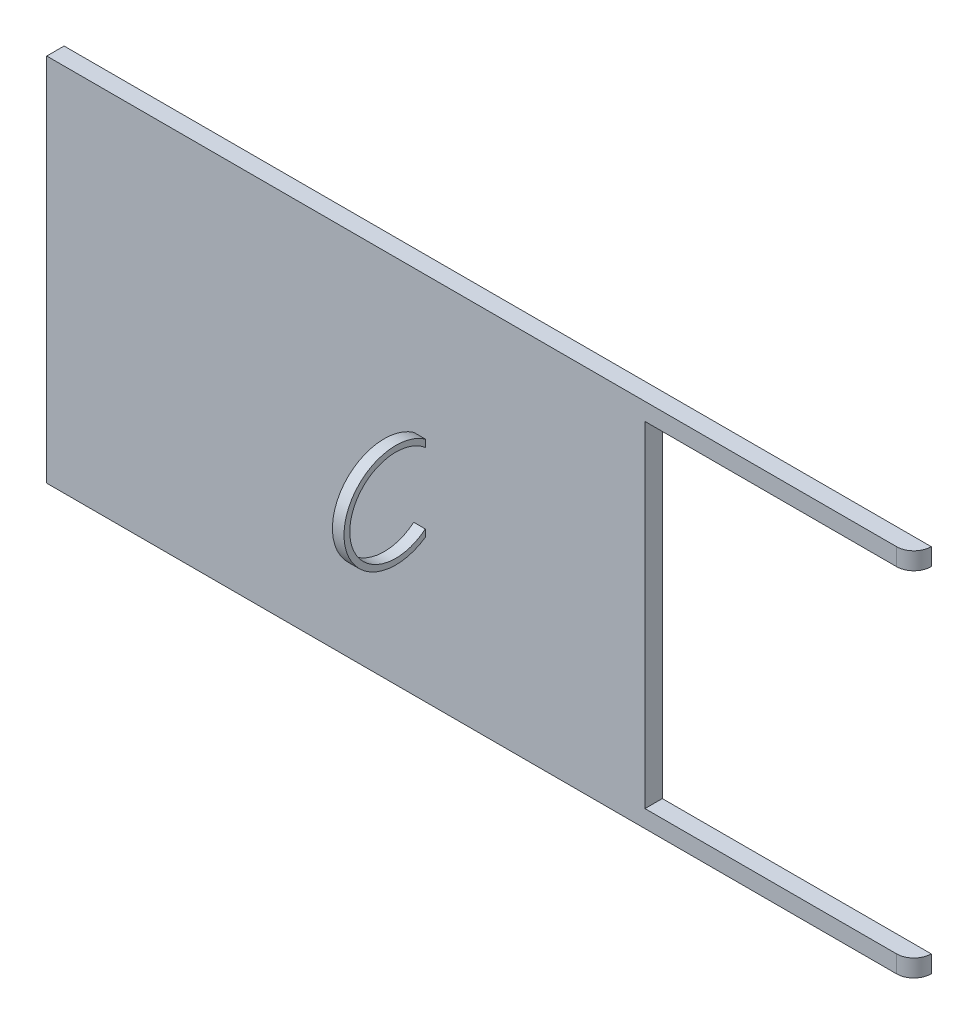
SolidWorks part; units mm, degrees
ref_plane "Top plane" through (0, 0, 0) normal (0, 0, 1) x (1, 0, 0)
ref_plane "Right plane" through (0, 0, 0) normal (0, 1, 0) x (1, 0, 0)
ref_plane "Front plane" through (0, 0, 0) normal (1, 0, 0) x (0, 0, -1)
sketch "Sketch1" plane through (0, 0, 0) normal (0, 0, 1) x (1, 0, 0)
  line L1 (-40, 113.7342) -> (63.4793, 113.7342)
  line L2 (-40, 113.7342) -> (-40, 49.7342)
  line L3 (-40, 49.7342) -> (63.4793, 49.7342)
  line L4 (63.4793, 113.7342) -> (63.4793, 49.7342)
extrude "Boss-Extrude1" add sketch "Sketch1" along normal blind 3
sketch "Sketch2" plane through (0, 0, 3) normal (0, 0, 1) x (1, 0, 0)
  line L0 (63.4793, 49.7342) -> (63.4793, 113.7342) construction
  line L1 (63.4793, 113.7342) -> (-40, 113.7342) construction
  line L2 (63.4793, 113.7342) -> (110, 113.7342)
  line L3 (63.4793, 113.7342) -> (63.4793, 110.7342)
  line L4 (63.4793, 110.7342) -> (110, 110.7342)
  line L5 (110, 113.7342) -> (110, 110.7342)
  line L7 (63.4793, 49.7342) -> (110, 49.7342)
  line L8 (63.4793, 49.7342) -> (63.4793, 52.7342)
  line L9 (63.4793, 52.7342) -> (110, 52.7342)
  line L10 (110, 49.7342) -> (110, 52.7342)
extrude "Boss-Extrude2" add sketch "Sketch2" against normal up to surface (3 mm away)
fillet "Fillet1" radius 3 2 edges at (110, 51.2342, 3) (110, 112.2342, 3)
ref_plane "Plane1" through (23.4793, 0, 0) normal (1, 0, 0) x (0, 0, -1)
sketch "Sketch3" plane through (23.4793, 0, 0) normal (1, 0, 0) x (0, 0, -1)
  line L4 (-3, 110.7342) -> (-3, 52.7342)
  line L5 (-3, 52.7342) -> (0, 52.7342)
  line L6 (0, 52.7342) -> (0, 110.7342)
  line L7 (0, 110.7342) -> (-3, 110.7342)
  line L8 (-3, 110.7342) -> (-3, 52.7342)
  line L9 (-3, 52.7342) -> (0, 52.7342)
  line L10 (0, 52.7342) -> (0, 110.7342)
  line L11 (0, 110.7342) -> (-3, 110.7342)
  circle A0 centre (-8.1024, 81.7345) radius 7.9589
  point P6 (-8.1024, 81.7345)
  dimension "D1" = 0
extrude "Extrude-Thin1" add sketch "Sketch3" along normal blind 2 thin contours A0 thin type one direction wall 1
